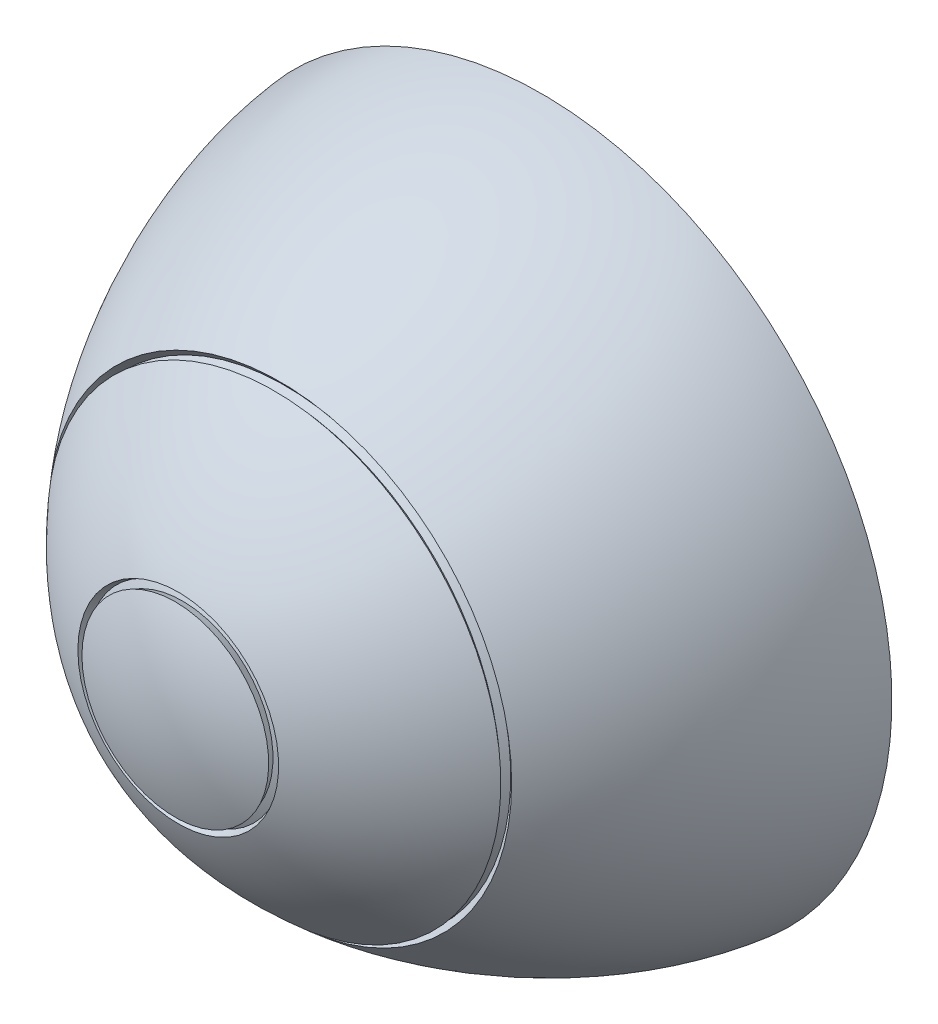
SolidWorks part; units mm, degrees
ref_plane "Plano frontal" through (0, 0, 0) normal (0, 0, 1) x (1, 0, 0)
ref_plane "Plano superior" through (0, 0, 0) normal (0, 1, 0) x (1, 0, 0)
ref_plane "Plano direito" through (0, 0, 0) normal (1, 0, 0) x (0, 0, -1)
sketch "Esboço1" plane through (0, 0, 0) normal (1, 0, 0) x (0, 0, -1)
  line L0 (-9.9, 0) -> (0, 0)
  line L1 (0, 0) -> (0, 9)
  spline S0 degree 3 poles (-9.9, 0) (-9.91, 4.8658) (-4.0304, 8.5987) (0, 9) knots 0 0 0 0 1 1 1 1
  dimension "D1" = 9.9
  dimension "D2" = 6.7
  dimension "D3" = 9
  dimension "D4" = 5.98
ref_axis "Eixo1" through (0, 0, -0.4952) along (0, 0, 1)
revolve "Revolução1" add sketch "Esboço1" angle 360 about axis through (0, 0, -0.4952) along (0, 0, 1)
sketch "Esboço2" plane through (0, 0, 0) normal (1, 0, 0) x (0, 0, -1)
  line L0 (-4, 5.47) -> (-4, 0)
  line L1 (-4, 0) -> (1, 0)
  line L2 (1, 0) -> (1, 7.0939)
  line L4 (0, -9) -> (0, 9) construction
  spline S2 degree 3 poles (3974.2479, 456.342) (-15.5269, 4.4582) (1.757, 7.1883) (0.0863, 6.9977) (0.0576, 6.9942) (-0.0275, 6.9834) (-0.0849, 6.9753) (-0.2579, 6.9486) (-0.3747, 6.9275) (-0.7278, 6.8556) (-0.9667, 6.7957) (-1.685, 6.5857) (-2.1656, 6.4053) (-3.5745, 5.7694) (-4.4722, 5.2198) (-6.0439, 3.9363) (-6.7188, 3.1972) (-7.4187, 2.0219) (-7.5992, 1.6204) (-7.7796, 1.0175) (-7.8247, 0.8164) (-7.8699, 0.5149) (-7.8812, 0.4144) (-7.8925, 0.2637) (-7.8953, 0.2134) (-7.8981, 0.138) (-7.8988, 0.1128) (-7.9247, -1.2513) (-6.9188, 19.5061) (-58.7823, -3999.0733) knots -0.447232 -0.447232 -0.447232 -0.447232 0.007812 0.007812 0.015625 0.015625 0.03125 0.03125 0.0625 0.0625 0.125 0.125 0.25 0.25 0.5 0.5 0.75 0.75 0.875 0.875 0.9375 0.9375 0.96875 0.96875 0.984375 0.984375 0.992187 0.992187 1.401925 1.401925 1.401925 1.401925 only from (0.2027, 7.0103) to (-7.9, 0.0066)
  spline S3 degree 3 poles (1, 7.0939) (0.2415, 7.0128) (0.21, 7.0118) (0.0863, 6.9977) (0.0576, 6.9942) (-0.0275, 6.9834) (-0.0849, 6.9753) (-0.2579, 6.9486) (-0.3747, 6.9275) (-0.7278, 6.8556) (-0.9667, 6.7957) (-1.685, 6.5857) (-2.1656, 6.4053) (-3.1034, 5.982) (-3.5612, 5.7395) (-4, 5.47) knots -0.018641 -0.018641 -0.018641 -0.018641 0.007812 0.007812 0.015625 0.015625 0.03125 0.03125 0.0625 0.0625 0.125 0.125 0.25 0.25 0.374606 0.374606 0.374606 0.374606
  dimension "D2" = 4
  dimension "D3" = 1
  dimension "D1" = 2
revolve "Corte-Revolução1" cut sketch "Esboço2" angle 360 about axis through (0, 0, -0.4952) along (0, 0, 1)
sketch "Esboço4" plane through (0, 0, 0) normal (1, 0, 0) x (0, 0, -1)
  line L0 (-7.0107, 5.9759) -> (-6.7463, 5.6757)
  line L1 (-6.8595, 6.1069) -> (-6.6, 5.8025)
  line L2 (0, -9) -> (0, 9) construction
  spline S2 degree 3 poles (-3999.4118, -40.7799) (28.7231, 1.649) (6.9582, 10.0935) (-0.3259, 9.1631) (-0.4021, 9.1523) (-0.6302, 9.1172) (-0.7814, 9.0899) (-1.2325, 8.9979) (-1.5299, 8.9232) (-2.411, 8.6655) (-2.9839, 8.4497) (-4.0966, 7.9475) (-4.6365, 7.6608) (-5.6762, 7.0215) (-6.1761, 6.6687) (-7.1229, 5.8955) (-7.57, 5.475) (-8.3886, 4.5618) (-8.7603, 4.0688) (-9.3909, 3.0097) (-9.6495, 2.443) (-9.916, 1.552) (-9.9846, 1.2485) (-10.0536, 0.7877) (-10.071, 0.6332) (-10.0884, 0.4007) (-10.0927, 0.3231) (-10.3453, -6.421) (1.732, -27.6599) (-387.2184, 3981.8953) knots -1.458458 -1.458458 -1.458458 -1.458458 0.015625 0.015625 0.03125 0.03125 0.0625 0.0625 0.125 0.125 0.25 0.25 0.375 0.375 0.5 0.5 0.625 0.625 0.75 0.75 0.875 0.875 0.9375 0.9375 0.96875 0.96875 0.984375 0.984375 2.325678 2.325678 2.325678 2.325678 only from (-0.0203, 9.199) to (-10.1, 0.013)
  spline S3 degree 3 poles (-6.8595, 6.1069) (-6.9103, 6.0636) (-6.9607, 6.02) (-7.0107, 5.9759) knots 0.518641 0.518641 0.518641 0.518641 0.532267 0.532267 0.532267 0.532267
  spline S4 degree 3 poles (3929.4892, 755.1603) (1.5793, -1.0598) (6.6732, 9.6539) (-0.2717, 8.7668) (-0.3445, 8.7565) (-0.5625, 8.7229) (-0.7074, 8.6967) (-1.1407, 8.6084) (-1.4275, 8.5364) (-2.279, 8.2874) (-2.8351, 8.078) (-4.4569, 7.346) (-5.479, 6.7216) (-6.8553, 5.5977) (-7.2874, 5.191) (-8.0755, 4.3119) (-8.4315, 3.8391) (-9.0323, 2.8301) (-9.2767, 2.2934) (-9.5275, 1.4548) (-9.5919, 1.1699) (-9.6566, 0.7381) (-9.6728, 0.5934) (-9.6891, 0.3758) (-9.6932, 0.3032) (-9.9301, -6.0216) (1.5144, 1.5831) (-389.5183, -3981.6952) knots -1.458825 -1.458825 -1.458825 -1.458825 0.015625 0.015625 0.03125 0.03125 0.0625 0.0625 0.125 0.125 0.25 0.25 0.5 0.5 0.625 0.625 0.75 0.75 0.875 0.875 0.9375 0.9375 0.96875 0.96875 0.984375 0.984375 2.328586 2.328586 2.328586 2.328586 only from (0.0203, 8.801) to (-9.7, 0.0118)
  spline S5 degree 3 poles (-6.6, 5.8025) (-6.6491, 5.7606) (-6.6979, 5.7184) (-6.7463, 5.6757) knots 0.518643 0.518643 0.518643 0.518643 0.53227 0.53227 0.53227 0.53227
  dimension "D3" = 6.6
  dimension "D4" = 0.2
  dimension "D1" = 0.2
  dimension "D2" = 0.2
revolve "Corte-Revolução2" cut sketch "Esboço4" angle 360 about axis through (0, 0, -0.4952) along (0, 0, 1)
sketch "Esboço5" plane through (0, 0, 0) normal (1, 0, 0) x (0, 0, -1)
  line L0 (-9.5287, 2.6603) -> (-9.1623, 2.5)
  line L1 (-9.6064, 2.476) -> (-9.2358, 2.3257)
  spline S2 degree 3 poles (-1861.988, -737.8447) (211.6916, -20.28) (6.8125, 32.5572) (-22.8655, -21.6254) (100.5201, -106.8277) (1970.3362, 260.0464) knots -14.099367 -14.099367 -14.099367 -14.099367 0.5 0.5 12.919484 12.919484 12.919484 12.919484 only from (-7.0107, 5.9759) to (-10.1, 0.0124)
  spline S3 degree 3 poles (-9.5287, 2.6603) (-9.5554, 2.5992) (-9.5813, 2.5377) (-9.6064, 2.476) knots 0.601092 0.601092 0.601092 0.601092 0.630456 0.630456 0.630456 0.630456
  spline S4 degree 3 poles (-1778.3365, -918.6636) (210.2869, -10.3448) (6.4855, 31.1275) (-22.574, -21.9259) (113.2844, -101.2857) (1982.4507, 149.9317) knots -14.205409 -14.205409 -14.205409 -14.205409 0.5 0.5 13.618662 13.618662 13.618662 13.618662 only from (-6.7463, 5.6757) to (-9.7, 0.0124)
  spline S5 degree 3 poles (-9.1623, 2.5) (-9.1877, 2.4422) (-9.2122, 2.3841) (-9.2358, 2.3257) knots 0.601134 0.601134 0.601134 0.601134 0.630513 0.630513 0.630513 0.630513
  dimension "D3" = 0.2
  dimension "D4" = 2.5
  dimension "D1" = 0.2
  dimension "D2" = 0.2
revolve "Corte-Revolução3" cut sketch "Esboço5" angle 360 about axis through (0, 0, -0.4952) along (0, 0, 1)
ref_axis "Eixo2" through (-9.9, 0, 0) along (1, 0, 0)
ref_axis "Eixo3" through (0, -9.9, 0) along (0, 1, 0)
